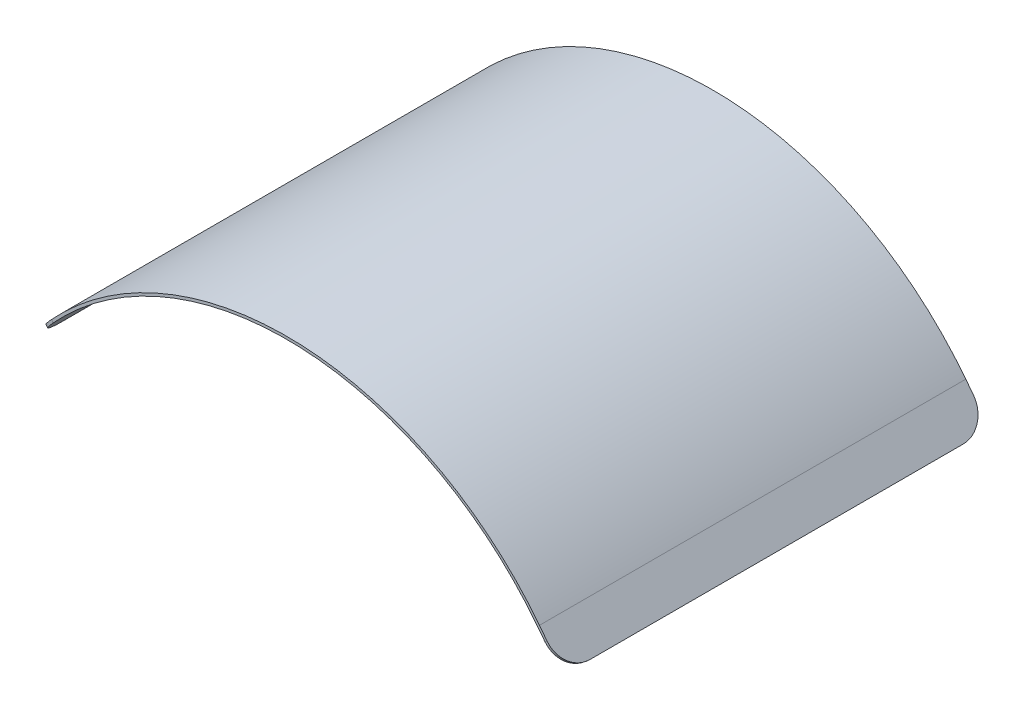
SolidWorks part; units mm, degrees
ref_plane "Front Plane" through (0, 0, 0) normal (0, 0, 1) x (1, 0, 0)
ref_plane "Top Plane" through (0, 0, 0) normal (0, 1, 0) x (1, 0, 0)
ref_plane "Right Plane" through (0, 0, 0) normal (1, 0, 0) x (0, 0, -1)
sketch "Sketch1" plane through (0, 0, 0) normal (0, 0, 1) x (1, 0, 0)
  line L0 (1897.37, 0) -> (1987.3089, -116.1111)
  line L1 (1889.4643, -6.1237) -> (1979.4032, -122.2348)
  line L2 (1987.3089, -116.1111) -> (1979.4032, -122.2348)
  line L3 (0, 0) -> (6.3263, -8.1673)
  line L4 (7.9057, -6.1237) -> (6.3263, -8.1673)
  arc A0 (0, 0) -> (1897.37, 0) centre (948.685, -734.8447) cw
  arc A1 (7.9057, -6.1237) -> (1889.4643, -6.1237) centre (948.685, -734.8447) cw
  dimension "D1" = 1200
  dimension "D2" = 1897.37
  dimension "D3" = 146.87
  dimension "D4" = 10
extrude "Boss-Extrude1" add sketch "Sketch1" along normal blind 1600 contours A0 L0 L2 L1 A1 L4 L3
fillet "Fillet1" radius 100 4 edges at (3.1632, -4.0836, 1600) (3.1632, -4.0836, 0) (1983.356, -119.173, 0) (1983.356, -119.173, 1600)
